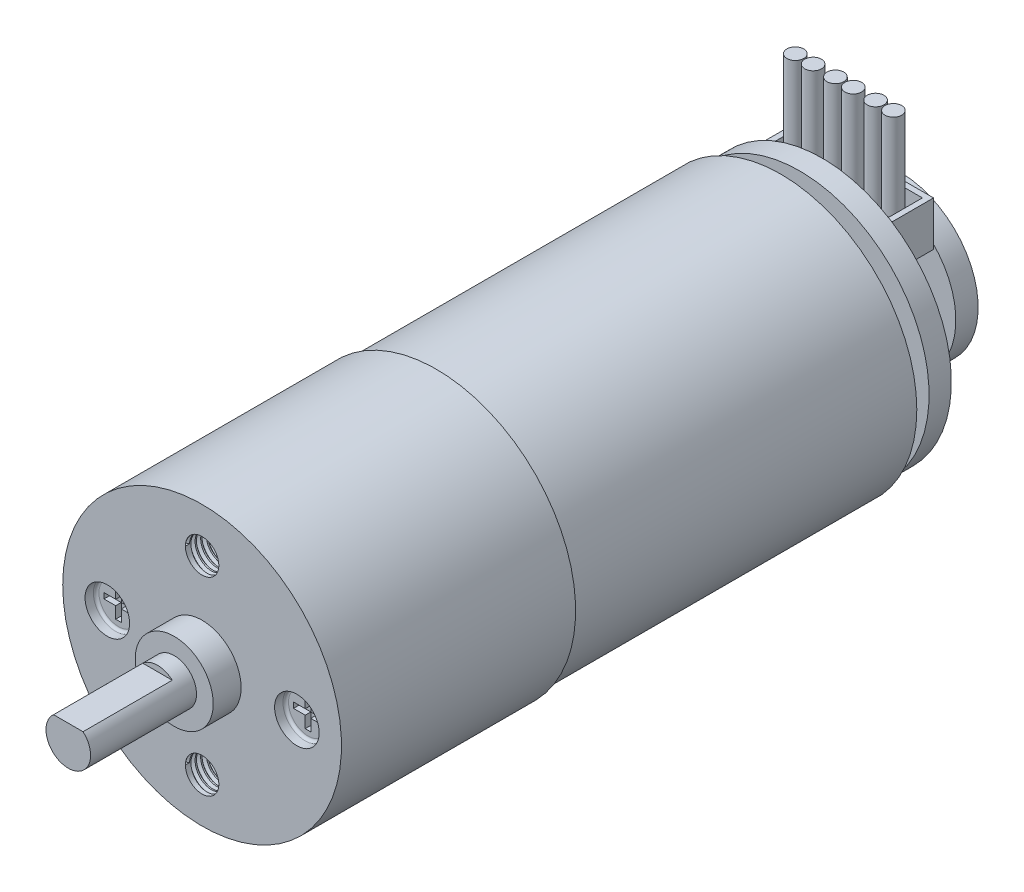
SolidWorks part; units mm, degrees
material "6063-T6"
ref_plane "Ön Düzlem" through (0, 0, 0) normal (0, 0, 1) x (1, 0, 0)
ref_plane "Üst Düzlem" through (0, 0, 0) normal (0, 1, 0) x (1, 0, 0)
ref_plane "Sağ Düzlem" through (0, 0, 0) normal (1, 0, 0) x (0, 0, -1)
sketch "Çizim2" plane through (0, 0, 0) normal (0, 0, 1) x (1, 0, 0)
  circle A0 centre (0, 0) radius 12.2
  dimension "D1" = 24.4
extrude "Yükseklik-Ekstrüzyon1" add sketch "Çizim2" along normal blind 30.8
sketch "Çizim3" plane through (0, 0, 30.8) normal (0, 0, 1) x (1, 0, 0)
  circle A0 centre (0, 0) radius 10
extrude "Yükseklik-Ekstrüzyon2" add sketch "Çizim3" along normal blind 0.1
sketch "Çizim4" plane through (0, 0, 30.9) normal (0, 0, 1) x (1, 0, 0)
  circle A0 centre (0, 0) radius 12.5
  dimension "D1" = 25
extrude "Yükseklik-Ekstrüzyon3" add sketch "Çizim4" along normal blind 21
ref_plane "Düzlem1" through (0, 0, 36.8) normal (0, 0, 1) x (1, 0, 0)
sketch "Çizim5" plane through (0, 0, 36.8) normal (0, 0, 1) x (1, 0, 0)
  circle A0 centre (0, 0) radius 13
  circle A1 centre (0, 0) radius 12.5
extrude "Kes-Ekstrüzyon1" [suppressed] cut sketch "Çizim5" against normal blind 1
ref_plane "Düzlem2" through (0, 0, 46.8) normal (0, 0, 1) x (1, 0, 0)
sketch "Çizim6" plane through (0, 0, 46.8) normal (0, 0, 1) x (1, 0, 0)
  circle A0 centre (0, 0) radius 13
  circle A1 centre (0, 0) radius 12.5
extrude "Kes-Ekstrüzyon2" [suppressed] cut sketch "Çizim6" along normal blind 1
sketch "Çizim7" plane through (0, 0, 51.9) normal (0, 0, 1) x (1, 0, 0)
  circle A0 centre (0, 0) radius 3.5
  circle A1 centre (0, 0) radius 2
  dimension "D1" = 7
extrude "Yükseklik-Ekstrüzyon4" add sketch "Çizim7" along normal blind 2.5
sketch "Çizim9" plane through (0, 0, 51.9) normal (0, 0, 1) x (1, 0, 0)
  circle A0 centre (0, 0) radius 2
extrude "Yükseklik-Ekstrüzyon5" add sketch "Çizim9" along normal blind 12
ref_plane "Düzlem3" through (0, 1.5, 0) normal (0, 1, 0) x (1, 0, 0)
sketch "Çizim10" plane through (0, 1.5, 0) normal (0, 1, 0) x (1, 0, 0)
  line L0 (2, -63.9) -> (2, -54.4) construction
  line L1 (-2, -63.9) -> (2, -63.9)
  line L2 (-2, -63.9) -> (-2, -55.9)
  line L3 (-2, -55.9) -> (2, -55.9)
  line L4 (2, -55.9) -> (2, -63.9)
  dimension "D1" = 8
extrude "Kes-Ekstrüzyon3" cut sketch "Çizim10" along normal blind 6.5
sketch "Çizim12" plane through (0, 0, 51.9) normal (0, 0, 1) x (1, 0, 0)
  circle A0 centre (0, 8.5) radius 1.5
  circle A1 centre (0, -8.5) radius 1.5
  dimension "D1" = 8.5
  dimension "D2" = 8.5
sketch "Çizim13" plane through (0, 0, 0) normal (0, 0, -1) x (-1, 0, 0)
  line L1 (-10.1, 0.15) -> (-8, 0.15)
  line L2 (-10.1, 0.15) -> (-10.1, -0.15)
  line L3 (-10.1, -0.15) -> (-8, -0.15)
  line L4 (-8, 0.15) -> (-8, -0.15)
  line L5 (-10.1, 0.15) -> (-8, -0.15) construction
  line L6 (-10.1, -0.15) -> (-8, 0.15) construction
  line L7 (8, 0.1293) -> (10.1, 0.1293)
  line L8 (8, 0.1293) -> (8, -0.1293)
  line L9 (8, -0.1293) -> (10.1, -0.1293)
  line L10 (10.1, 0.1293) -> (10.1, -0.1293)
  line L11 (8, 0.1293) -> (10.1, -0.1293) construction
  line L12 (8, -0.1293) -> (10.1, 0.1293) construction
  point P0 (-9.05, 0)
  point P5 (9.05, 0)
  point P10 (8, 0)
  dimension "D1" = 9.05
  dimension "D2" = 9.05
extrude "Yükseklik-Ekstrüzyon6" add sketch "Çizim13" along normal blind 4
extrude "Kes-Ekstrüzyon5" cut sketch "Çizim12" against normal blind 4
sketch "Çizim14" plane through (0, 0, 51.9) normal (0, 0, 1) x (1, 0, 0)
  circle A0 centre (-8.5, 0) radius 2
  circle A1 centre (8.5, 0) radius 2
  dimension "D1" = 17
  dimension "D2" = 8.5
extrude "Kes-Ekstrüzyon6" cut sketch "Çizim14" against normal blind 1
sketch "Çizim16" plane through (0, 0, 51.9) normal (0, 0, 1) x (1, 0, 0)
  line L1 (8.75, -0.25) -> (8.75, -1.3)
  line L2 (-8.75, 1.3) -> (-8.75, 0.25)
  line L3 (-8.25, 1.3) -> (-8.25, 0.25)
  line L4 (-9.8, -0.25) -> (-8.75, -0.25)
  line L5 (-9.8, 0.25) -> (-8.75, 0.25)
  line L6 (-8.25, 1.3) -> (-8.75, 1.3)
  line L7 (-9.8, 0.25) -> (-9.8, -0.25)
  line L8 (-8.75, -1.3) -> (-8.25, -1.3)
  line L9 (-7.2, 0.25) -> (-7.2, -0.25)
  line L10 (8.25, -0.25) -> (7.2, -0.25)
  line L11 (-8.25, 0.25) -> (-7.2, 0.25)
  line L12 (8.25, -0.25) -> (8.25, -1.3)
  line L13 (-8.25, -0.25) -> (-8.25, -1.3)
  line L14 (8.25, 0.25) -> (7.2, 0.25)
  line L15 (7.2, 0.25) -> (7.2, -0.25)
  line L16 (-8.25, -0.25) -> (-7.2, -0.25)
  line L17 (8.75, -1.3) -> (8.25, -1.3)
  line L18 (-8.75, -0.25) -> (-8.75, -1.3)
  line L19 (9.8, 0.25) -> (9.8, -0.25)
  line L20 (8.25, 1.3) -> (8.75, 1.3)
  line L21 (9.8, 0.25) -> (8.75, 0.25)
  line L22 (9.8, -0.25) -> (8.75, -0.25)
  line L23 (8.25, 1.3) -> (8.25, 0.25)
  line L24 (8.75, 1.3) -> (8.75, 0.25)
extrude "Kes-Ekstrüzyon10" cut sketch "Çizim16" against normal blind 1.5
fillet "Radyus2" radius 0.25 2 edges at (10.5, 0, 50.9) (-6.5, 0, 50.9)
sketch "Çizim17" plane through (0, 0, 0) normal (0, 0, -1) x (-1, 0, 0)
  circle A0 centre (0, 0) radius 4
extrude "Yükseklik-Ekstrüzyon7" add sketch "Çizim17" along normal blind 1.7
sketch "Çizim18" plane through (0, 0, -1.7) normal (0, 0, -1) x (-1, 0, 0)
  circle A0 centre (0, 0) radius 11.6
  dimension "D1" = 23.2
extrude "Yükseklik-Ekstrüzyon8" add sketch "Çizim18" along normal blind 2
sketch "Çizim19" plane through (0, 0, -3.7) normal (0, 0, -1) x (-1, 0, 0)
  circle A0 centre (0, 0) radius 2
extrude "Yükseklik-Ekstrüzyon9" add sketch "Çizim19" along normal blind 5
sketch "Çizim20" plane through (0, 0, -3.7) normal (0, 0, -1) x (-1, 0, 0)
  line L2 (-6, 9.5) -> (6, 9.5)
  line L3 (-6, 9.5) -> (-6, 5.5)
  line L4 (-6, 5.5) -> (6, 5.5)
  line L5 (6, 9.5) -> (6, 5.5)
  line L6 (-6, 9.5) -> (6, 5.5) construction
  line L7 (-6, 5.5) -> (6, 9.5) construction
extrude "Yükseklik-Ekstrüzyon10" add sketch "Çizim20" along normal blind 4
sketch "Çizim22" plane through (0, 9.5, 0) normal (0, 1, 0) x (1, 0, 0)
  line L1 (-5.5, 7.2) -> (5.5, 7.2)
  line L2 (-5.5, 7.2) -> (-5.5, 4.2)
  line L3 (-5.5, 4.2) -> (5.5, 4.2)
  line L4 (5.5, 7.2) -> (5.5, 4.2)
  line L5 (-5.5, 7.2) -> (5.5, 4.2) construction
  line L6 (-5.5, 4.2) -> (5.5, 7.2) construction
  line L8 (-6, 7.7) -> (-6, 3.7) construction
  line L10 (-6, 7.7) -> (6, 7.7) construction
  point P0 (0, 5.7)
  dimension "D1" = 0.5
  dimension "D2" = 11
  dimension "D3" = 0.5
  dimension "D4" = 3
extrude "Kes-Ekstrüzyon11" cut sketch "Çizim22" against normal blind 3
sketch "Çizim23" plane through (0, 6.5, 0) normal (0, 1, 0) x (1, 0, 0)
  line L5 (5.5, 4.2) -> (5.5, 7.2) construction
  circle A0 centre (-4.4, 5.7) radius 0.75
  circle A1 centre (-2.8, 5.7) radius 0.75
  circle A2 centre (-0.8, 5.7) radius 0.75
  circle A3 centre (0.8, 5.7) radius 0.75
  circle A4 centre (2.8, 5.7) radius 0.75
  circle A5 centre (4.4, 5.7) radius 0.75
  dimension "D3" = 1.5
  dimension "D4" = 1.5
  dimension "D6" = 1.5
  dimension "D7" = 1.5
  dimension "D10" = 1.5
  dimension "D11" = 1.5
  dimension "D13" = 1.1
  dimension "D2" = 1.6
  dimension "D5" = 2
  dimension "D8" = 1.6
  dimension "D9" = 2
  dimension "D12" = 1.6
extrude "Yükseklik-Ekstrüzyon12" add sketch "Çizim23" along normal blind 10
sketch "Çizim26" plane through (0, 0, -8.7) normal (0, 0, -1) x (-1, 0, 0)
  circle A0 centre (0, 0) radius 7
  dimension "D1" = 14
extrude "Yükseklik-Ekstrüzyon13" add sketch "Çizim26" along normal blind 2
sketch "Çizim27" plane through (0, 0, -10.7) normal (0, 0, -1) x (-1, 0, 0)
  circle A0 centre (0, 0) radius 5
extrude "Yükseklik-Ekstrüzyon14" add sketch "Çizim27" along normal blind 0.5
sketch "Çizim28" plane through (0, 0, -11.2) normal (0, 0, -1) x (-1, 0, 0)
  circle A0 centre (0, 0) radius 1
extrude "Yükseklik-Ekstrüzyon15" add sketch "Çizim28" along normal blind 0.5
thread "Thread1" pitch 0.5 method cut profile "Thread Profile2" start angle 0, offset 0, length 0, pitch 0.5, diameter 3
ref_plane "Plane2" through (-1.5, 8.5, 51.9) normal (0, -1, 0) x (-1, 0, 0)
sketch "Thread Profile2" plane through (-1.5, 8.5, 51.9) normal (0, -1, 0) x (-1, 0, 0)
  line L0 (0, 0) -> (0, 0.5) construction
  line L1 (0, 0) -> (0.2706, 0.1562)
  line L2 (0.2706, 0.1562) -> (0.2706, 0.2187)
  line L3 (0.2706, 0.2187) -> (0, 0.375)
  line L4 (0.2706, 0.1875) -> (0, 0.1875) construction
  line L11 (0, 0) -> (0, 0.375)
  point P2 (0, 0)
  dimension "Pitch" = 0.5
  dimension "Profile_Angle" = 60
  dimension "Profile_Land" = 0.0625
  dimension "Profile_Height" = 0.2706
thread "Thread2" pitch 0.5 method cut profile "Thread Profile3" start angle 0, offset 0, length 0, pitch 0.5, diameter 3
ref_plane "Plane3" through (-1.5, -8.5, 51.9) normal (0, -1, 0) x (-1, 0, 0)
sketch "Thread Profile3" plane through (-1.5, -8.5, 51.9) normal (0, -1, 0) x (-1, 0, 0)
  line L0 (0, 0) -> (0, 0.5) construction
  line L1 (0, 0) -> (0.2706, 0.1562)
  line L2 (0.2706, 0.1562) -> (0.2706, 0.2187)
  line L3 (0.2706, 0.2187) -> (0, 0.375)
  line L4 (0.2706, 0.1875) -> (0, 0.1875) construction
  line L11 (0, 0) -> (0, 0.375)
  point P2 (0, 0)
  dimension "Pitch" = 0.5
  dimension "Profile_Angle" = 60
  dimension "Profile_Land" = 0.0625
  dimension "Profile_Height" = 0.2706
ref_plane "Face" through (0, 0, 51.9) normal (0, 0, 1) x (1, 0, 0)
ref_axis "Axle" through (0, 0, 54.4) along (0, 0, -1)
